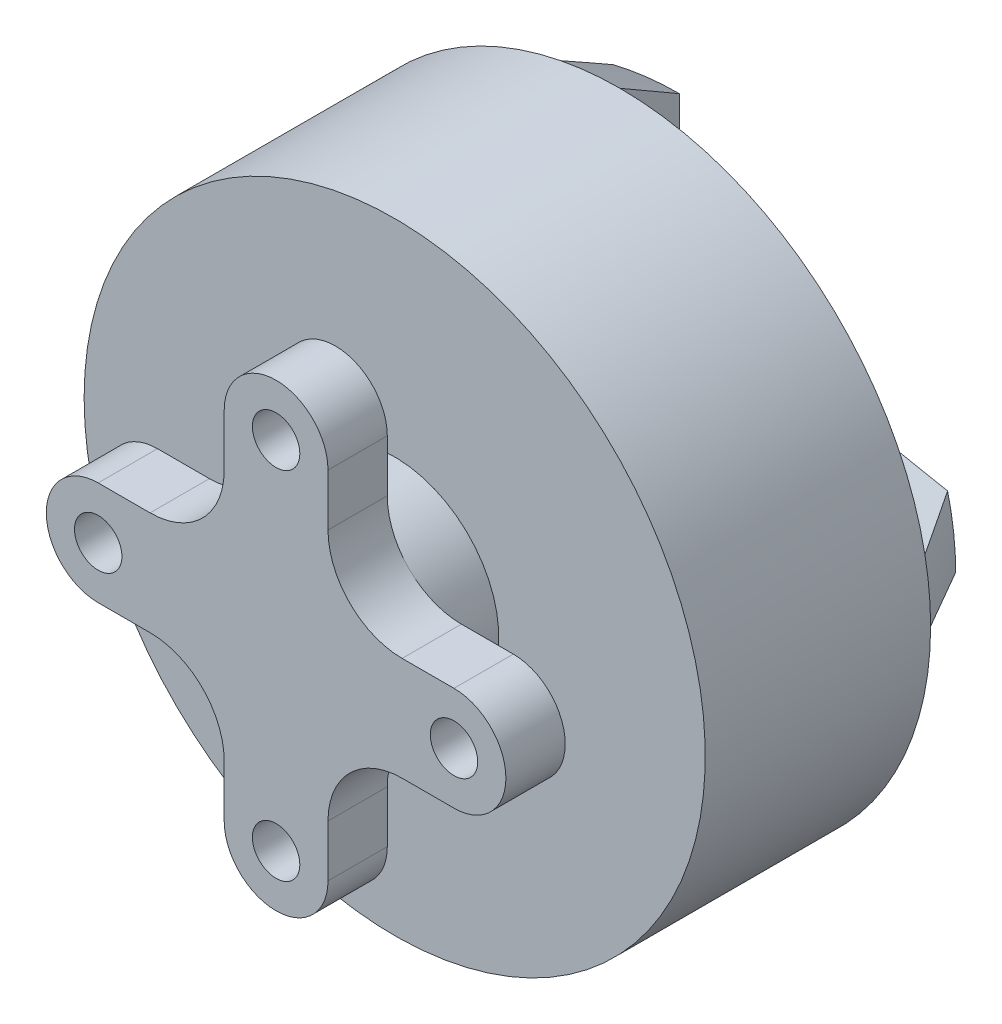
SolidWorks part; units mm, degrees
ref_plane "Front Plane" through (0, 0, 0) normal (1, 0, 0) x (0, 1, 0)
ref_plane "Top Plane" through (0, 0, 0) normal (0, 0, 1) x (0, 1, 0)
ref_plane "Right Plane" through (0, 0, 0) normal (0, 1, 0) x (-1, 0, 0)
sketch "Sketch1" plane through (0, 0, 0) normal (0, 0, 1) x (0, 1, 0)
  line L0 (-1.75, 1.75) -> (-1.75, 6)
  line L2 (1.75, 6) -> (1.75, 1.75)
  line L13 (0, 0) -> (1.5513, 0) construction
  line L16 (0, 0) -> (0, 1.4954) construction
  line L17 (1.75, 1.75) -> (6, 1.75)
  line L18 (6, -1.75) -> (1.75, -1.75)
  line L19 (1.75, -1.75) -> (1.75, -6)
  line L20 (-1.75, -6) -> (-1.75, -1.75)
  line L21 (-1.75, -1.75) -> (-6, -1.75)
  line L22 (-6, 1.75) -> (-1.75, 1.75)
  circle A2 centre (0, 6) radius 0.8
  arc A4 (1.75, 6) -> (-1.75, 6) centre (0, 6) ccw
  circle A5 centre (6, 0) radius 0.8
  arc A6 (6, -1.75) -> (6, 1.75) centre (6, 0) ccw
  circle A7 centre (0, -6) radius 0.8
  arc A8 (-1.75, -6) -> (1.75, -6) centre (0, -6) ccw
  circle A9 centre (-6, 0) radius 0.8
  arc A10 (-6, 1.75) -> (-6, -1.75) centre (-6, 0) ccw
  point P10 (5.2, 0)
  point P21 (0, -5.2)
  point P26 (0, 5.2)
  point P29 (-5.2, 0)
  point P35 (0, 0)
  dimension "D2" = 1.6
  dimension "D3" = 1.75
  dimension "D1" = 10.4
  dimension "D4" = 4
extrude "Boss-Extrude1" add sketch "Sketch1" along normal blind 2
fillet "Fillet2" radius 2.5 4 edges at (1.75, 1.75, 1) (1.75, -1.75, 1) (-1.75, -1.75, 1) (-1.75, 1.75, 1)
sketch "Sketch2" plane through (0, 0, 0) normal (0, 0, -1) x (1, 0, 0)
  circle A0 centre (0, 0) radius 3.5104
  arc A2 (1.75, 4.25) -> (4.25, 1.75) centre (4.25, 4.25) ccw construction
extrude "Boss-Extrude2" add sketch "Sketch2" along normal blind 2
sketch "Sketch3" plane through (0, 0, 0) normal (0, 0, 1) x (0, 1, 0)
  circle A0 centre (0, 0) radius 10.475
  dimension "D1" = 20.95
extrude "Boss-Extrude3" add sketch "Sketch3" against normal blind 7.6 from surface starting at face at (-3.5104, 0, -2)
sketch "Sketch4" plane through (0, 0, -9.6) normal (0, 0, -1) x (1, 0, 0)
  circle A0 centre (0, 0) radius 8.475
  circle A1 centre (0, 0) radius 10.475 construction
  dimension "D1" = 2
extrude "Cut-Extrude1" cut sketch "Sketch4" against normal blind 2
sketch "Sketch5" plane through (0, 0, -9.6) normal (0, 0, -1) x (1, 0, 0)
  line L0 (0, 0) -> (-4, 0)
  line L1 (-4, 0) -> (-2, -10.2823)
  line L2 (0, 0) -> (0, -10.475)
  line L3 (-1.7, -1.7) -> (-1.7, 0) construction
  line L4 (-1.7, -1.7) -> (0, -1.7) construction
  line L5 (-1.7, 1.7) -> (-1.412, 1.7) construction
  line L6 (-1.7, 1.7) -> (-1.7, 1.535) construction
  line L7 (-1.7, -0.95) -> (-1.7, 0) construction
  line L8 (-1.7, 0.95) -> (-1.7, 0) construction
  circle A0 centre (0, 0) radius 10.475 construction
  circle A2 centre (-1.7, -1.7) radius 0.75
  circle A3 centre (-1.7, 1.7) radius 0.75 construction
  circle A7 centre (0, 0) radius 10.475
  arc A8 (-2, -10.2823) -> (0, -10.475) centre (0, 0) ccw
  point P12 (-1.7, -0.95)
  point P13 (-1.7, 0.95)
  dimension "D1" = 1.5
  dimension "D2" = 1.9
  dimension "D3" = 2
  dimension "D4" = 4
  dimension "D6" = 0
extrude "Boss-Extrude4" add sketch "Sketch5" along normal blind 2
chamfer "Chamfer1" distance 2 angle 30 1 edges at (-1.0046, 10.4267, -11.6) first distance on face at (-0.5, 5.1893, -10.6)
pattern_circular "CirPattern2" count 4 over 360 about axis through (0, 0, -7.6) along (0, 0, -1) of "Chamfer1", "Boss-Extrude4"
sketch "Sketch6" plane through (0, 0, -11.6) normal (0, 0, -1) x (1, 0, 0)
  circle A0 centre (0, 0) radius 0.73
  dimension "D1" = 1.46
extrude "Boss-Extrude5" add sketch "Sketch6" along normal blind 3.5
